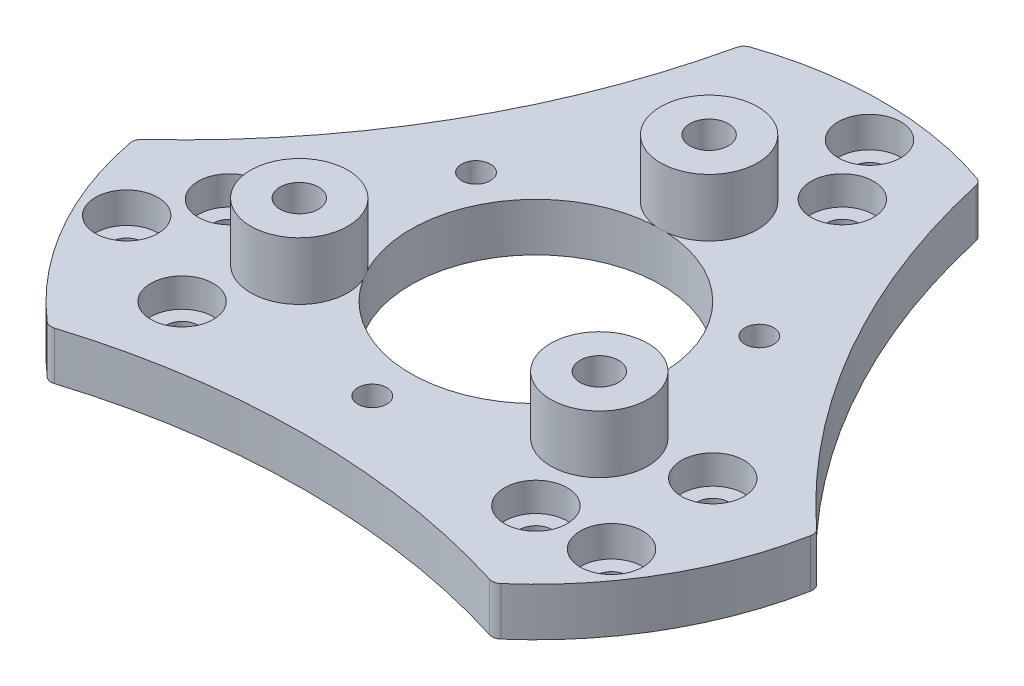
SolidWorks part; units mm, degrees
ref_plane "Front Plane" through (0, 0, 0) normal (0, 0, 1) x (1, 0, 0)
ref_plane "Top Plane" through (0, 0, 0) normal (0, 1, 0) x (1, 0, 0)
ref_plane "Right Plane" through (0, 0, 0) normal (1, 0, 0) x (0, 0, -1)
sketch "Sketch1" plane through (0, 0, 0) normal (0, 1, 0) x (1, 0, 0)
  circle A0 centre (0, 0) radius 36
  circle A1 centre (0, 0) radius 13
  dimension "D1" = 72
  dimension "D2" = 26
extrude "Boss-Extrude1" add sketch "Sketch1" along normal blind 5
sketch "Sketch2" plane through (0, 5, 0) normal (0, 1, 0) x (1, 0, 0)
  line L0 (0, -1000) -> (0, 49000) construction
  line L1 (2.789, 31.8782) -> (0, 0) construction
  circle A0 centre (2.789, 31.8782) radius 1.65
  dimension "D1" = 3.3
  dimension "D2" = 32
  dimension "D3" = 5
extrude "Cut-Extrude1" cut sketch "Sketch2" against normal through all
pattern_circular "CirPattern1" count 3 over 360 about axis through (0, 5, 0) along (0, -1, 0) of "Cut-Extrude1" reverse direction yes
sketch "Sketch10" plane through (0, 5, 0) normal (0, 1, 0) x (1, 0, 0)
  line L0 (0, 0) -> (17101.0072, 46984.631) construction
  line L1 (0, 0) -> (-17101.0072, 46984.631) construction
  line L2 (0, 0) -> (0, 50000) construction
  line L3 (-9.5766, 26.3114) -> (-12.3127, 33.8289)
  line L4 (9.5766, 26.3114) -> (12.3127, 33.8289)
  line L5 (17.9981, -21.4492) -> (23.1404, -27.5776)
  line L6 (27.5746, -4.8621) -> (35.4531, -6.2513)
  line L7 (-27.5746, -4.8621) -> (-35.4531, -6.2513)
  line L8 (-17.9981, -21.4492) -> (-23.1404, -27.5776)
  arc A0 (-12.3127, 33.8289) -> (12.3127, 33.8289) centre (0, 0) cw
  circle A1 centre (0, 0) radius 36 construction
  arc A2 (-9.5766, 26.3114) -> (9.5766, 26.3114) centre (0, 0) cw
  arc A3 (35.4531, -6.2513) -> (23.1404, -27.5776) centre (0, 0) cw
  arc A4 (27.5746, -4.8621) -> (17.9981, -21.4492) centre (0, 0) cw
  arc A5 (-23.1404, -27.5776) -> (-35.4531, -6.2513) centre (0, 0) cw
  arc A6 (-17.9981, -21.4492) -> (-27.5746, -4.8621) centre (0, 0) cw
  point P26 (0, 0)
  dimension "D1" = 20
  dimension "D2" = 20
  dimension "D3" = 8
  dimension "D4" = 3
sketch "Sketch3" plane through (0, 5, 0) normal (0, 1, 0) x (1, 0, 0)
  line L0 (0, 0) -> (86.6025, 50) construction
  line L1 (-1000, 0) -> (49000, 0) construction
  circle A0 centre (86.6025, 50) radius 76.0295
  dimension "D3" = 100
extrude "Cut-Extrude2" cut sketch "Sketch3" against normal blind 10
pattern_circular "CirPattern2" count 3 over 360 about axis through (0, 5, 0) along (0, -1, 0) of "Cut-Extrude2"
fillet "Fillet1" radius 1 6 edges at (23.1404, 2.5, 27.5776) (-23.1404, 2.5, 27.5776) (-35.4531, 2.5, 6.2513) (-12.3127, 2.5, -33.8289) (35.4531, 2.5, 6.2513) (12.3127, 2.5, -33.8289)
sketch "Sketch4" plane through (0, 5, 0) normal (0, 1, 0) x (1, 0, 0)
  circle A0 centre (0, 0) radius 6 construction
  circle A1 centre (0, 18) radius 12 construction
  circle A2 centre (0, 18) radius 5.05
  dimension "D1" = 12
  dimension "D2" = 24
  dimension "D3" = 10.1
extrude "Boss-Extrude2" add sketch "Sketch4" along normal blind 6
sketch "Sketch7" plane through (0, 5, 0) normal (0, 1, 0) x (1, 0, 0)
  circle A0 centre (2.789, 31.8782) radius 3.25
  dimension "D1" = 6.5
extrude "Cut-Extrude5" cut sketch "Sketch7" against normal blind 3.2
pattern_circular "CirPattern3" count 3 over 360 about axis through (0, 5, 0) along (0, -1, 0) of "Cut-Extrude5", "Boss-Extrude2" reverse direction yes
sketch "Sketch8" plane through (0, 5, 0) normal (0, 1, 0) x (1, 0, 0)
  line L0 (14.7224, 8.5) -> (0, 0) construction
  line L1 (-1000, 0) -> (49000, 0) construction
  circle A0 centre (14.7224, 8.5) radius 1.5
  dimension "D3" = 3
  dimension "D1" = 30
  dimension "D2" = 17
extrude "Cut-Extrude6" cut sketch "Sketch8" against normal blind 10
sketch "Sketch12" plane through (0, 11, 0) normal (0, 1, 0) x (1, 0, 0)
  circle A0 centre (0, 18) radius 2
  dimension "D1" = 4
extrude "Cut-Extrude8" cut sketch "Sketch12" against normal through all
pattern_circular "CirPattern4" count 3 over 360 about axis through (0, 5, 0) along (0, -1, 0) of "Cut-Extrude6", "Cut-Extrude8" reverse direction yes
sketch "Sketch9" plane through (0, 5, 0) normal (0, 1, 0) x (1, 0, 0)
  line L0 (-5.7304, 32.4987) -> (0, 0) construction
  line L1 (-25.7839, 33.0244) -> (49214.6038, 8715.4333) construction
  line L2 (-23.1208, 32.4785) -> (49217.2669, 8714.8874) construction
  line L3 (0, -1000) -> (0, 49000) construction
  circle A0 centre (-5.7304, 32.4987) radius 4 construction
  circle A1 centre (-5.7304, 32.4987) radius 1.65
  arc A2 (11.7835, 34.0169) -> (-11.7835, 34.0169) centre (0, 0) ccw construction
  dimension "D1" = 8
  dimension "D2" = 3.3
  dimension "D3" = 1
  dimension "D4" = 10
sketch "Sketch13" plane through (0, 5, 0) normal (0, 1, 0) x (1, 0, 0)
  line L0 (6.7293, 25.1141) -> (0, 0) construction
  line L1 (0, 0) -> (0, 18) construction
  line L2 (-6.7293, 25.1141) -> (0, 0) construction
  circle A0 centre (6.7293, 25.1141) radius 1.7
  circle A1 centre (-6.7293, 25.1141) radius 1.7
  dimension "D1" = 3.4
  dimension "D2" = 26
  dimension "D3" = 15
extrude "Cut-Extrude9" cut sketch "Sketch13" against normal through all
pattern_circular "CirPattern5" count 3 over 360 about axis through (0, 5, 0) along (0, -1, 0) of "Cut-Extrude9" reverse direction yes
sketch "Sketch14" plane through (0, 5, 0) normal (0, 1, 0) x (1, 0, 0)
  circle A3 centre (-18.3848, -18.3848) radius 3.25
  circle A4 centre (-25.1141, -6.7293) radius 3.25
  circle A5 centre (-6.7293, 25.1141) radius 3.25
  circle A6 centre (6.7293, 25.1141) radius 3.25
  circle A7 centre (25.1141, -6.7293) radius 3.25
  circle A8 centre (18.3848, -18.3848) radius 3.25
  dimension "D1" = 6.5
extrude "Cut-Extrude10" cut sketch "Sketch14" against normal blind 3
